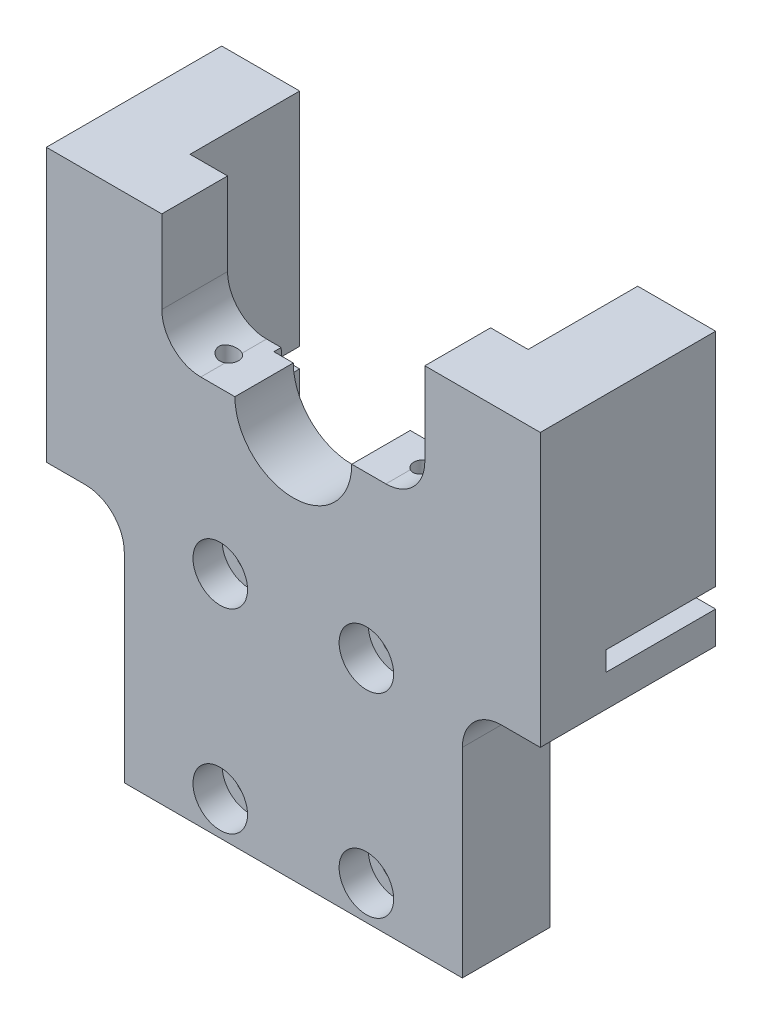
SolidWorks part; units mm, degrees
ref_plane "Front Plane" through (0, 0, 0) normal (0, 0, 1) x (1, 0, 0)
ref_plane "Top Plane" through (0, 0, 0) normal (0, 1, 0) x (1, 0, 0)
ref_plane "Right Plane" through (0, 0, 0) normal (1, 0, 0) x (0, 0, -1)
sketch "Sketch1" plane through (0, 0, 0) normal (0, 0, 1) x (1, 0, 0)
  line L1 (44.5, -23.75) -> (-0.5, -23.75)
  line L2 (44.5, -23.75) -> (44.5, 23.75)
  line L3 (44.5, 23.75) -> (-44.5, 23.75)
  line L4 (-44.5, -23.75) -> (-44.5, 23.75)
  line L5 (44.5, -23.75) -> (-44.5, 23.75) construction
  line L6 (44.5, 23.75) -> (-44.5, -23.75) construction
  line L10 (7.5, 11.75) -> (-32.5, 11.75) construction
  line L12 (-0.5, -23.75) -> (-44.5, -23.75)
  point P0 (0, 0)
  dimension "D1" = 47.5
  dimension "D2" = 89
  dimension "D8" = 40
  dimension "D10" = 12
  dimension "D11" = 12
extrude "Boss-Extrude1" add sketch "Sketch1" along normal mid plane 9
fillet "Fillet1" [suppressed] radius 5
fillet "Fillet2" [suppressed] radius 10
sketch "Sketch2" plane through (0, 0, 4.5) normal (0, 0, 1) x (1, 0, 0)
  line L1 (-44.5, 23.75) -> (-44.5, -23.75) construction
  line L8 (0, 0) -> (0, 23.75) construction
  line L9 (44.5, 23.75) -> (-44.5, 23.75) construction
  line L16 (-44.5, -23.75) -> (44.5, -23.75) construction
  line L17 (18.5, -23.75) -> (21.5, -23.75) construction
  line L18 (18.5, -23.75) -> (18.5, 4.75) construction
  line L19 (20, 3.25) -> (21.5, 3.25) construction
  line L20 (21.5, -23.75) -> (21.5, 4.75) construction
  line L22 (18.5, 4.75) -> (18.5, 3.25) construction
  line L23 (18.5, 3.25) -> (20, 3.25) construction
  line L24 (21.5, 4.75) -> (21.5, 3.25) construction
  line L31 (44.5, -23.75) -> (44.5, 23.75) construction
  line L32 (44.5, 14.25) -> (38, 14.25)
  line L33 (38, 14.25) -> (38, 2.25)
  line L34 (38, 2.25) -> (39.75, 2.25)
  line L35 (39.75, 2.25) -> (39.75, 12.5)
  line L36 (39.75, 12.5) -> (44.5, 12.5)
  line L37 (44.5, 12.5) -> (44.5, 14.25)
  line L38 (-44.5, -23.75) -> (44.5, -23.75) construction
  line L39 (-38, 2.25) -> (-39.75, 2.25)
  line L40 (-39.75, 2.25) -> (-39.75, 12.5)
  line L41 (-39.75, 12.5) -> (-44.5, 12.5)
  line L42 (-44.5, 12.5) -> (-44.5, 14.25)
  line L43 (-44.5, 14.25) -> (-38, 14.25)
  line L44 (-38, 14.25) -> (-38, 2.25)
  arc A8 (18.5, 4.75) -> (21.5, 4.75) centre (20, 4.75) ccw construction
  arc A9 (21.5, 4.75) -> (18.5, 4.75) centre (20, 4.75) ccw construction
  dimension "D5" = 12
  dimension "D6" = 26
  dimension "D1" = 66
  dimension "D2" = 82.5
  dimension "D3" = 1.75
  dimension "D4" = 1.75
  dimension "D8" = 3
  dimension "D9" = 30
extrude "Cut-Extrude1" [suppressed] cut sketch "Sketch2" against normal through all
sketch "Sketch4" plane through (0, 0, 4.5) normal (0, 0, 1) x (1, 0, 0)
  line L0 (44.5, 23.75) -> (-44.5, 23.75) construction
  line L1 (21.5, 23.75) -> (57.0092, 23.75)
  line L2 (21.5, 23.75) -> (21.5, -24.7621)
  line L3 (21.5, -24.7621) -> (57.0092, -24.7621)
  line L4 (57.0092, 23.75) -> (57.0092, -24.7621)
  line L5 (-44.5, 23.75) -> (-44.5, -23.75) construction
  dimension "D1" = 66
  dimension "D2" = 48.5121
  dimension "D3" = 35.5092
extrude "Cut-Extrude2" cut sketch "Sketch4" against normal blind 10
sketch "Sketch5" [suppressed] plane through (0, 0, 2.5) normal (0, 0, 1) x (1, 0, 0)
  line L0 (-38, 2.25) -> (-39.75, 2.25) construction
  line L1 (-38, 14.25) -> (-38, 2.25) construction
  line L2 (-39.75, 2.25) -> (-39.75, 12.5) construction
  line L3 (-39.75, 12.5) -> (-44.5, 12.5) construction
  line L4 (-44.5, 12.5) -> (-44.5, 14.25) construction
  line L5 (-44.5, 14.25) -> (-38, 14.25) construction
  line L6 (-38, 2.25) -> (-39.75, 2.25)
  line L7 (-38, 14.25) -> (-38, 2.25)
  line L8 (-39.75, 2.25) -> (-39.75, 12.5)
  line L9 (-39.75, 12.5) -> (-44.5, 12.5)
  line L10 (-44.5, 12.5) -> (-44.5, 14.25)
  line L11 (-44.5, 14.25) -> (-38, 14.25)
  line L12 (-11.5, 23.75) -> (-11.5, -39.7083) construction
  line L13 (11.5, 23.75) -> (-34.5, 23.75) construction
  line L14 (16.75, 2.25) -> (16.75, 12.5)
  line L15 (15, 14.25) -> (15, 2.25)
  line L16 (15, 2.25) -> (16.75, 2.25)
  line L17 (21.5, 14.25) -> (15, 14.25)
  line L18 (21.5, 12.5) -> (21.5, 14.25)
  line L19 (16.75, 12.5) -> (21.5, 12.5)
  arc A0 (-24.5, -27.75) -> (-0.5, -27.75) centre (-12.5, -27.75) ccw construction
extrude "Cut-Extrude3" [suppressed] cut sketch "Sketch5" against normal blind 10
sketch "Sketch6" plane through (0, 0, 4.5) normal (0, 0, 1) x (1, 0, 0)
  line L0 (21.5, 23.75) -> (-44.5, 23.75) construction
  line L1 (21.5, 23.75) -> (44.5, 23.75)
  line L2 (21.5, 23.75) -> (21.5, -23.75)
  line L3 (21.5, -23.75) -> (44.5, -23.75)
  line L4 (44.5, 23.75) -> (44.5, -23.75)
  line L5 (21.5, 23.75) -> (21.5, -23.75) construction
  dimension "D1" = 23
fillet "Fillet5" [suppressed] radius 10
sketch "Sketch8" plane through (0, 23.75, 0) normal (0, 1, 0) x (1, 0, 0)
  line L4 (-44.5, -4.5) -> (21.5, -4.5)
  line L5 (21.5, -4.5) -> (21.5, 4.5)
  line L6 (21.5, 4.5) -> (-44.5, 4.5)
  line L7 (-44.5, 4.5) -> (-44.5, -4.5)
  line L8 (-44.5, -4.5) -> (21.5, -4.5)
  line L9 (21.5, -4.5) -> (21.5, 4.5)
  line L10 (21.5, 4.5) -> (-44.5, 4.5)
  line L11 (-44.5, 4.5) -> (-44.5, -4.5)
  dimension "D1" = 0
extrude "Boss-Extrude3" add sketch "Sketch8" along normal blind 5
sketch "Sketch9" plane through (0, 28.75, 0) normal (0, 1, 0) x (1, 0, 0)
  line L0 (-44.5, 4.5) -> (-44.5, -4.5) construction
  line L1 (-44.5, -4.5) -> (-28.5, -4.5)
  line L2 (-44.5, -4.5) -> (-44.5, 11.5)
  line L3 (-44.5, 11.5) -> (-28.5, 11.5)
  line L4 (-28.5, -4.5) -> (-28.5, 11.5)
  line L5 (-44.5, -4.5) -> (21.5, -4.5) construction
  line L6 (-11.5, 4.5) -> (-11.5, -4.5) construction
  line L7 (21.5, 4.5) -> (-44.5, 4.5) construction
  line L8 (21.5, 11.5) -> (5.5, 11.5)
  line L9 (5.5, -4.5) -> (5.5, 11.5)
  line L10 (21.5, -4.5) -> (5.5, -4.5)
  line L11 (21.5, -4.5) -> (21.5, 11.5)
  dimension "D1" = 16
  dimension "D2" = 16
extrude "Boss-Extrude4" [suppressed] add sketch "Sketch9" against normal blind 3
sketch "Sketch10" [suppressed] plane through (0, 28.75, 0) normal (0, 1, 0) x (1, 0, 0)
  line L0 (-44.5, 10.5) -> (-39.6498, 10.5)
  line L1 (-44.5, 13.5) -> (-44.5, -2.5) construction
  line L2 (-28.5, 13.5) -> (-44.5, 13.5) construction
  line L3 (-39.6498, 10.5) -> (-39.6498, 3)
  line L4 (-39.6498, 3) -> (-41.6498, 3)
  line L5 (-41.6498, 3) -> (-41.6498, 8.5)
  line L6 (-41.6498, 8.5) -> (-44.5, 8.5)
  line L7 (-44.5, 8.5) -> (-44.5, 10.5)
  line L8 (-11.5, -2.5) -> (-11.5, 2.5) construction
  line L9 (-44.5, -2.5) -> (21.5, -2.5) construction
  line L10 (5.5, 2.5) -> (-28.5, 2.5) construction
  line L11 (21.5, 10.5) -> (16.6498, 10.5)
  line L12 (21.5, 8.5) -> (21.5, 10.5)
  line L13 (18.6498, 8.5) -> (21.5, 8.5)
  line L14 (18.6498, 3) -> (18.6498, 8.5)
  line L15 (16.6498, 3) -> (18.6498, 3)
  line L16 (16.6498, 10.5) -> (16.6498, 3)
  dimension "D1" = 3
  dimension "D2" = 2
  dimension "D3" = 2
  dimension "D4" = 7.5
  dimension "D5" = 2.8502
extrude "Cut-Extrude5" [suppressed] cut sketch "Sketch10" against normal blind 5
fillet "Fillet7" radius 10 2 edges at (21.5, 28.75, 0) (-44.5, 28.75, 0)
sketch "Sketch16" plane through (0, 0, 4.5) normal (0, 0, 1) x (1, 0, 0)
  line L0 (-19, -0.25) -> (-19, -20.25) construction
  line L1 (-19, -20.25) -> (-4, -20.25) construction
  line L2 (-4, -20.25) -> (-4, -0.25) construction
  line L3 (-4, -0.25) -> (-19, -0.25) construction
  line L4 (-44.5, 18.75) -> (-44.5, -23.75) construction
  line L5 (-44.5, -23.75) -> (21.5, -23.75) construction
  line L6 (21.5, 18.75) -> (21.5, -23.75) construction
  circle A0 centre (-19, -0.25) radius 1.5
  circle A1 centre (-4, -0.25) radius 1.5
  circle A2 centre (-19, -20.25) radius 1.5
  circle A3 centre (-4, -20.25) radius 1.5
  dimension "D1" = 3
  dimension "D2" = 20
  dimension "D3" = 15
  dimension "D4" = 3.5
  dimension "D5" = 25.5
extrude "Cut-Extrude6" cut sketch "Sketch16" against normal blind 10
sketch "Sketch17" plane through (0, 0, -4.5) normal (0, 0, -1) x (-1, 0, 0)
  line L0 (44.5, -23.75) -> (-21.5, -23.75) construction
  line L1 (44.5, -23.75) -> (28.85, -23.75)
  line L2 (44.5, -23.75) -> (44.5, 28.75)
  line L3 (44.5, 28.75) -> (28.85, 28.75)
  line L4 (28.85, -23.75) -> (28.85, 28.75)
  line L5 (-11.5, 28.75) -> (34.5, 28.75) construction
  line L6 (44.5, 18.75) -> (44.5, -23.75) construction
  line L7 (11.5, -23.75) -> (11.5, 28.75) construction
  line L8 (-21.5, -23.75) -> (-5.85, -23.75)
  line L9 (-5.85, -23.75) -> (-5.85, 28.75)
  line L10 (-21.5, 28.75) -> (-5.85, 28.75)
  line L11 (-21.5, -23.75) -> (-21.5, 28.75)
  dimension "D1" = 15.65
extrude "Cut-Extrude7" cut sketch "Sketch17" against normal blind 10
sketch "Sketch18" plane through (0, 0, 4.5) normal (0, 0, 1) x (1, 0, 0)
  line L0 (-11.5, 28.75) -> (-11.5, -23.75) construction
  line L1 (-28.85, 28.75) -> (5.85, 28.75) construction
  line L2 (-28.85, -23.75) -> (5.85, -23.75) construction
  circle A0 centre (-11.5, 16.25) radius 6
  dimension "D1" = 12
  dimension "40" = 40
extrude "Cut-Extrude8" cut sketch "Sketch18" against normal blind 10
sketch "Sketch20" plane through (0, 0, 4.5) normal (0, 0, 1) x (1, 0, 0)
  line L0 (-28.85, -23.75) -> (-28.85, 28.75) construction
  line L1 (-28.85, 0.75) -> (-36.85, 0.75)
  line L2 (-28.85, 0.75) -> (-28.85, 28.75)
  line L3 (-28.85, 28.75) -> (-36.85, 28.75)
  line L4 (-36.85, 0.75) -> (-36.85, 28.75)
  line L5 (5.85, 28.75) -> (5.85, -23.75) construction
  line L6 (5.85, 0.75) -> (13.85, 0.75)
  line L7 (5.85, 0.75) -> (5.85, 28.75)
  line L8 (5.85, 28.75) -> (13.85, 28.75)
  line L9 (13.85, 0.75) -> (13.85, 28.75)
  line L11 (-28.85, 28.75) -> (5.85, 28.75) construction
  dimension "D1" = 8
  dimension "D2" = 28
extrude "Boss-Extrude5" add sketch "Sketch20" against normal blind 18
sketch "Sketch22" plane through (0, 0, 4.5) normal (0, 0, 1) x (1, 0, 0)
  line L0 (-25, 16.25) -> (2, 16.25)
  line L1 (2, 16.25) -> (2, 28.75)
  line L2 (-36.85, 28.75) -> (13.85, 28.75) construction
  line L3 (-25, 28.75) -> (-25, 16.25)
  line L4 (-36.85, 28.75) -> (-36.85, 0.75) construction
  circle A0 centre (-11.5, 16.25) radius 8 construction
  point P12 (-11.5, 16.25)
  dimension "D3" = 12.5
  dimension "D4" = 25.35
  dimension "D5" = 16
  dimension "D1" = 27
extrude "Cut-Extrude10" cut sketch "Sketch22" against normal blind 9 and the other way through all
sketch "Sketch23" plane through (0, 0, -4.5) normal (0, 0, -1) x (-1, 0, 0)
  line L0 (-13.85, 0.75) -> (-13.85, 28.75) construction
  line L1 (28.85, -23.75) -> (-5.85, -23.75) construction
  circle A0 centre (11.5, 16.25) radius 8
  dimension "D1" = 16
  dimension "D2" = 25.35
  dimension "D3" = 40
extrude "Cut-Extrude11" cut sketch "Sketch23" against normal blind 3
sketch "Sketch24" plane through (13.85, 0, 0) normal (1, 0, 0) x (0, 0, -1)
  line L0 (-4.5, 6.05) -> (13.5, 6.05) construction
  line L1 (-4.5, 0.75) -> (-4.5, 28.75) construction
  line L2 (13.5, 0.75) -> (13.5, 28.75) construction
  line L3 (13.5, 0.75) -> (-4.5, 0.75) construction
  line L4 (2.25, 6.05) -> (13.5, 6.05)
  line L5 (2.25, 6.05) -> (2.25, 4.05)
  line L6 (2.25, 4.05) -> (13.5, 4.05)
  line L7 (13.5, 6.05) -> (13.5, 4.05)
  dimension "D1" = 2
  dimension "D2" = 3.3
  dimension "D4" = 6.75
extrude "Cut-Extrude12" cut sketch "Sketch24" against normal blind 8 and the other way blind 68.0001 from offset 42.7 offset against normal yes
sketch "Sketch25" plane through (0, 16.25, 0) normal (0, 1, 0) x (1, 0, 0)
  line L0 (-1.5, -1.125) -> (-21.5, -1.125) construction
  line L2 (2, -4.5) -> (2, 4.5) construction
  line L3 (-5.5, -4.5) -> (2, -4.5) construction
  circle A0 centre (-1.5, -1.125) radius 1
  circle A1 centre (-21.5, -1.125) radius 1
  point P4 (-1.5, -1.125)
  dimension "D1" = 2
  dimension "D2" = 20
  dimension "D4" = 3.5
  dimension "D3" = 3.375
extrude "Cut-Extrude13" cut sketch "Sketch25" against normal blind 12.5
sketch "Sketch26" plane through (0, 0, -4.5) normal (0, 0, -1) x (-1, 0, 0)
  line L9 (-5.85, 6.05) -> (28.85, 6.05)
  line L10 (28.85, 6.05) -> (28.85, 28.75)
  line L11 (28.85, 28.75) -> (25, 28.75)
  line L12 (25, 28.75) -> (25, 16.25)
  line L13 (25, 16.25) -> (19.5, 16.25)
  line L14 (3.5, 16.25) -> (-2, 16.25)
  line L15 (-2, 16.25) -> (-2, 28.75)
  line L16 (-2, 28.75) -> (-5.85, 28.75)
  line L17 (-5.85, 28.75) -> (-5.85, 6.05)
  line L18 (-5.85, 6.05) -> (28.85, 6.05)
  line L19 (28.85, 6.05) -> (28.85, 28.75)
  line L20 (28.85, 28.75) -> (25, 28.75)
  line L21 (25, 28.75) -> (25, 16.25)
  line L22 (25, 16.25) -> (19.5, 16.25)
  line L23 (3.5, 16.25) -> (-2, 16.25)
  line L24 (-2, 16.25) -> (-2, 28.75)
  line L25 (-2, 28.75) -> (-5.85, 28.75)
  line L26 (-5.85, 28.75) -> (-5.85, 6.05)
  arc A1 (3.5, 16.25) -> (19.5, 16.25) centre (11.5, 16.25) ccw
  arc A2 (3.5, 16.25) -> (19.5, 16.25) centre (11.5, 16.25) ccw
  dimension "D1" = 0
extrude "Cut-Extrude15" cut sketch "Sketch26" against normal blind 2.25
fillet "Fillet8" radius 4 4 edges at (2, 16.25, 1.125) (-25, 16.25, 1.125) (-28.85, 0.75, 0) (5.85, 0.75, 0)
sketch "Sketch27" plane through (0, 0, -4.5) normal (0, 0, -1) x (-1, 0, 0)
  line L0 (28.85, -23.75) -> (-5.85, -23.75) construction
  line L1 (22.35, -23.75) -> (0.65, -23.75)
  line L2 (22.35, -23.75) -> (22.35, -16.25)
  line L3 (22.35, -16.25) -> (0.65, -16.25)
  line L4 (0.65, -23.75) -> (0.65, -16.25)
  line L5 (28.85, -3.25) -> (28.85, -23.75) construction
  line L6 (28.85, -10.25) -> (-5.85, -10.25) construction
  line L7 (-5.85, -23.75) -> (-5.85, -3.25) construction
  line L8 (0.65, 3.25) -> (0.65, -4.25)
  line L9 (22.35, 3.25) -> (0.65, 3.25)
  line L10 (22.35, -4.25) -> (0.65, -4.25)
  line L11 (22.35, 3.25) -> (22.35, -4.25)
  point P10 (-5.85, -10.25)
  dimension "D1" = 7.5
  dimension "D2" = 21.7
  dimension "D3" = 6.5
  dimension "D4" = 13.5
extrude "Cut-Extrude16" cut sketch "Sketch27" against normal blind 0.4
chamfer "Chamfer1" distance 0.4 angle 45 1 edges at (-11.5, -4.25, -4.1)
chamfer "Chamfer2" distance 0.4 angle 45 1 edges at (-11.5, -16.25, -4.1)
sketch "Sketch28" plane through (0, 0, 4.5) normal (0, 0, 1) x (1, 0, 0)
  line L0 (-19, -0.25) -> (-19, -20.25) construction
  line L1 (-19, -20.25) -> (-4, -20.25) construction
  line L2 (-4, -20.25) -> (-4, -0.25) construction
  line L3 (-4, -0.25) -> (-19, -0.25) construction
  line L4 (-28.85, -23.75) -> (-28.85, -3.25) construction
  line L5 (-28.85, -23.75) -> (5.85, -23.75) construction
  circle A0 centre (-19, -0.25) radius 2.8
  circle A1 centre (-4, -0.25) radius 2.8
  circle A2 centre (-4, -20.25) radius 2.8
  circle A3 centre (-19, -20.25) radius 2.8
  dimension "D1" = 5.6
  dimension "D2" = 15
  dimension "D3" = 20
  dimension "D4" = 9.85
  dimension "D5" = 3.5
extrude "Cut-Extrude17" cut sketch "Sketch28" against normal blind 3
sketch "Sketch29" plane through (0, 0, -4.5) normal (0, 0, -1) x (-1, 0, 0)
  line L0 (0.65, -4.25) -> (22.35, -4.25) construction
  line L1 (0.65, 3.25) -> (0.65, -4.25) construction
  line L2 (22.35, -3.85) -> (22.35, 3.25) construction
  line L3 (-5.85, 4.05) -> (28.85, 4.05) construction
  line L4 (0.65, 3.25) -> (22.35, 3.25)
  line L5 (0.65, 3.25) -> (0.65, 4.05)
  line L6 (0.65, 4.05) -> (22.35, 4.05)
  line L7 (22.35, 3.25) -> (22.35, 4.05)
  line L8 (22.35, -4.25) -> (22.35, 3.25) construction
  line L9 (22.35, -16.25) -> (0.65, -16.25) construction
  line L11 (0.65, -16.25) -> (0.65, -23.75) construction
  line L12 (22.35, -23.75) -> (22.35, -16.25) construction
  circle A0 centre (2.65, -4.25) radius 2
  circle A1 centre (20.35, -4.25) radius 2
  circle A2 centre (2.65, -16.25) radius 2
  circle A3 centre (20.35, -16.25) radius 2
  dimension "D1" = 4
extrude "Cut-Extrude18" cut sketch "Sketch29" against normal blind 0.4
